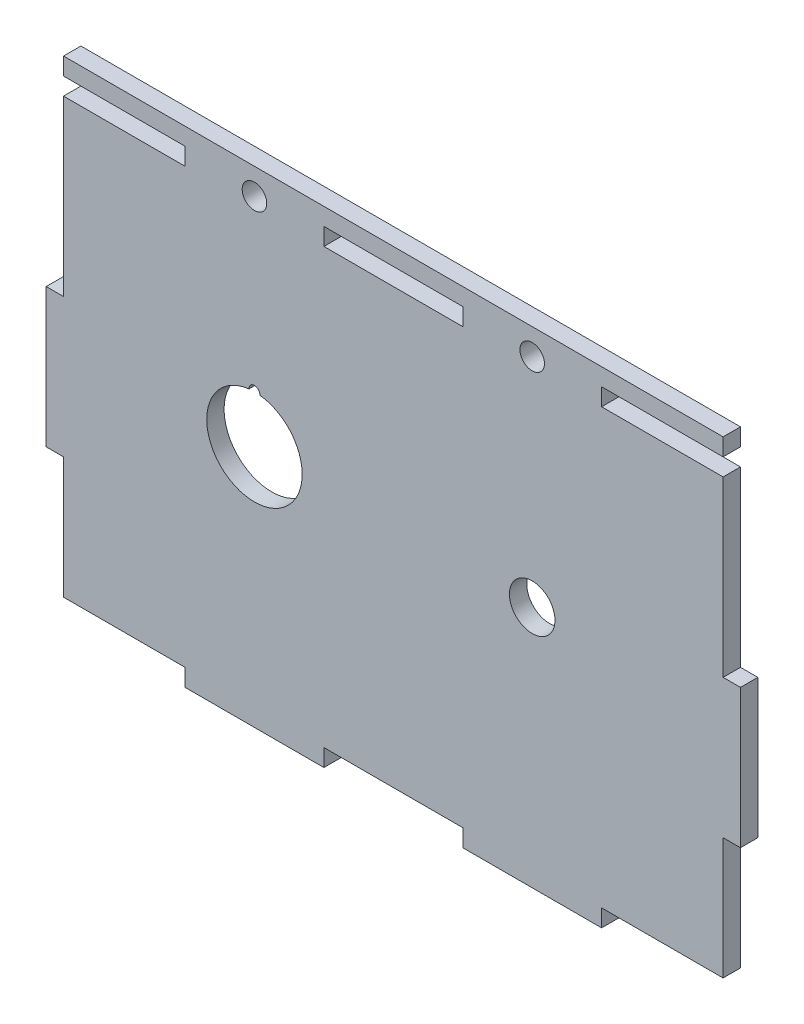
SolidWorks part; units mm, degrees
ref_plane "Front Plane" through (0, 0, 0) normal (0, 0, 1) x (1, 0, 0)
ref_plane "Top Plane" through (0, 0, 0) normal (0, 1, 0) x (1, 0, 0)
ref_plane "Right Plane" through (0, 0, 0) normal (1, 0, 0) x (0, 0, -1)
sketch "Sketch1" plane through (0, 0, 0) normal (0, 0, 1) x (1, 0, 0)
  line L1 (0, 0) -> (127, 0)
  line L2 (0, 0) -> (0, 88.9)
  line L3 (0, 88.9) -> (127, 88.9)
  line L4 (127, 0) -> (127, 88.9)
  dimension "D1" = 127
  dimension "D2" = 88.9
extrude "Boss-Extrude1" add sketch "Sketch1" along normal blind 3.175
sketch "Sketch5" plane through (0, 0, 3.175) normal (0, 0, 1) x (1, 0, 0)
  line L1 (0, 0) -> (3.175, 0)
  line L2 (0, 0) -> (0, 25.4)
  line L3 (0, 25.4) -> (3.175, 25.4)
  line L4 (3.175, 0) -> (3.175, 25.4)
  dimension "D1" = 25.4
  dimension "D2" = 3.175
extrude "Cut-Extrude4" cut sketch "Sketch5" against normal blind 6.35
sketch "Sketch6" plane through (0, 0, 3.175) normal (0, 0, 1) x (1, 0, 0)
  line L1 (0, 0) -> (25.4, 0)
  line L2 (0, 0) -> (0, 3.175)
  line L3 (0, 3.175) -> (25.4, 3.175)
  line L4 (25.4, 0) -> (25.4, 3.175)
  dimension "D1" = 3.175
  dimension "D2" = 25.4
extrude "Cut-Extrude5" cut sketch "Sketch6" against normal blind 6.35
pattern_linear "LPattern5" count 2 spacing 50.8 along (0, 1, 0) count 2 spacing 123.825 along (1, 0, 0) of "Cut-Extrude4"
pattern_linear "LPattern6" count 3 spacing 50.8 along (1, 0, 0) count 2 spacing 82.55 along (0, 1, 0) of "Cut-Extrude5"
hole_wizard "#8 Clearance Hole1" positions "Sketch10" profile "Sketch9" hole size "#8" standard "ANSI Inch"
sketch "Sketch10" plane through (0, 0, 3.175) normal (0, 0, 1) x (1, 0, 0)
  line L2 (25.4, 82.55) -> (25.4, 85.725) construction
  line L3 (76.2, 85.725) -> (50.8, 85.725) construction
  line L4 (76.2, 82.55) -> (76.2, 85.725) construction
  point P0 (38.1, 84.1375)
  point P2 (88.9, 84.1375)
  point P10 (25.4, 84.1375)
  dimension "D1" = 12.7
  dimension "D3" = 12.7
  dimension "D4" = 1.5875
sketch "Sketch9" plane through (38.1, 84.1375, 3.175) normal (1, 0, 0) x (0, -1, 0)
  line L0 (0, 0) -> (0, 11.5107)
  line L1 (0, 11.5107) -> (2.2479, 10.16)
  line L2 (2.2479, 10.16) -> (2.2479, 0)
  line L5 (2.2479, 0) -> (0, 0)
  line L10 (0, 11.5107) -> (-2.2479, 10.16) construction
  line L11 (0, -6.35) -> (0, 107.95) construction
  dimension "Hole Dia." = 4.4958
  dimension "Hole Depth" = 10.16
  dimension "Drill Angle" = 118
sketch "Sketch11" plane through (0, 0, 3.175) normal (0, 0, 1) x (1, 0, 0)
  line L1 (0, 88.9) -> (3.175, 88.9)
  line L2 (0, 88.9) -> (0, 76.2)
  line L3 (0, 76.2) -> (3.175, 76.2)
  line L4 (3.175, 88.9) -> (3.175, 76.2)
  line L5 (127, 88.9) -> (123.825, 88.9)
  line L6 (127, 88.9) -> (127, 76.2)
  line L7 (127, 76.2) -> (123.825, 76.2)
  line L8 (123.825, 88.9) -> (123.825, 76.2)
extrude "Cut-Extrude6" cut sketch "Sketch11" against normal blind 7.62
sketch "Sketch12" plane through (0, 0, 3.175) normal (0, 0, 1) x (1, 0, 0)
  line L0 (0, 50.8) -> (0, 25.4) construction
  line L2 (25.4, 0) -> (50.8, 0) construction
  circle A0 centre (38.1, 44.45) radius 8.7312
  circle A1 centre (38.1, 53.1812) radius 1
  dimension "D1" = 17.4625
  dimension "D2" = 2
  dimension "D3" = 38.1
  dimension "D4" = 44.45
extrude "Cut-Extrude7" cut sketch "Sketch12" against normal blind 7.62 contours A1 A0 | A0 A1 | A0 A1 region at (38.1, 44.3966, 3.175) region at (38.1, 52.7467, 3.175) region at (38.1, 53.5952, 3.175)
sketch "Sketch13" plane through (0, 0, 3.175) normal (0, 0, 1) x (1, 0, 0)
  line L0 (127, 25.4) -> (127, 50.8) construction
  line L2 (76.2, 0) -> (101.6, 0) construction
  circle A0 centre (88.9, 44.45) radius 4.1672
  dimension "D1" = 8.3344
  dimension "D2" = 38.1
  dimension "D3" = 44.45
extrude "Cut-Extrude8" cut sketch "Sketch13" against normal blind 7.62
